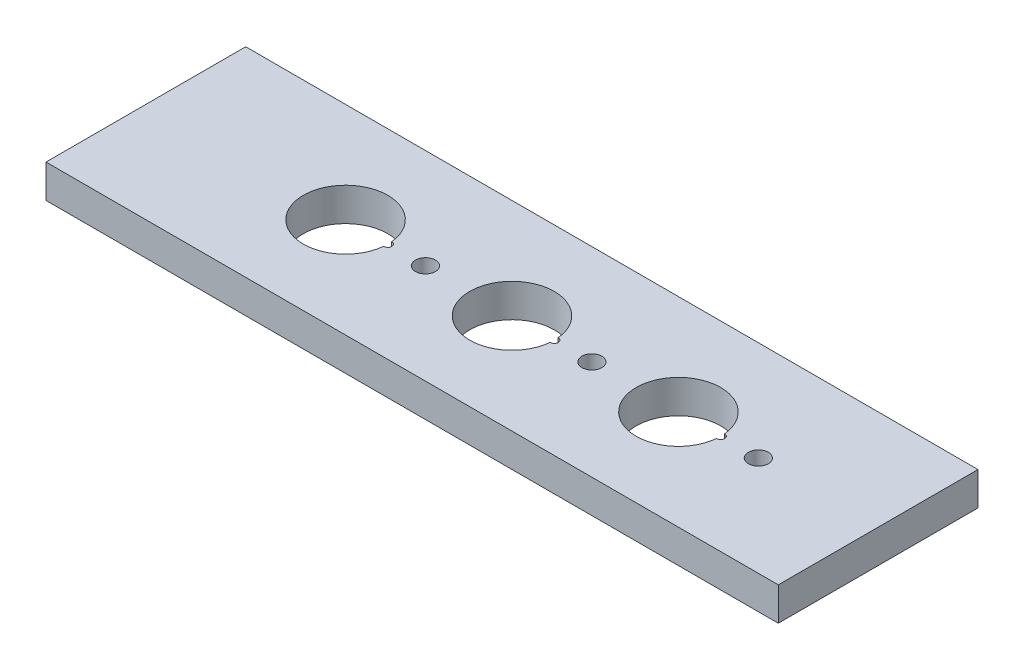
SolidWorks part; units mm, degrees
ref_plane "Front Plane" through (0, 0, 0) normal (0, 0, 1) x (1, 0, 0)
ref_plane "Top Plane" through (0, 0, 0) normal (0, 1, 0) x (1, 0, 0)
ref_plane "Right Plane" through (0, 0, 0) normal (1, 0, 0) x (0, 0, -1)
sketch "Sketch1" plane through (0, 0, 0) normal (0, 1, 0) x (1, 0, 0)
  line L1 (-55, 15) -> (55, 15)
  line L2 (-55, 15) -> (-55, -15)
  line L3 (-55, -15) -> (55, -15)
  line L4 (55, 15) -> (55, -15)
  circle A0 centre (25, 0) radius 6.35 construction
  arc A1 (31.3217, 0.5993) -> (31.3217, -0.5993) centre (31.35, 0) cw
  arc A2 (31.3217, 0.5993) -> (31.3217, -0.5993) centre (25, 0) ccw
  arc A3 (6.3217, 0.5993) -> (6.3217, -0.5993) centre (6.35, 0) cw
  arc A4 (6.3217, 0.5993) -> (6.3217, -0.5993) centre (0, 0) ccw
  arc A5 (-18.6783, 0.5993) -> (-18.6783, -0.5993) centre (-18.65, 0) cw
  arc A6 (-18.6783, 0.5993) -> (-18.6783, -0.5993) centre (-25, 0) ccw
  circle A7 centre (37, 0) radius 1.5
  circle A8 centre (12, 0) radius 1.5
  circle A9 centre (-13, 0) radius 1.5
  point P4 (0, 15)
  point P6 (55, 0)
  dimension "D3" = 12.7
  dimension "D4" = 0.6
  dimension "D7" = 3
  dimension "D1" = 110
  dimension "D2" = 30
  dimension "D6" = 25
  dimension "D8" = 12
  dimension "D5" = 3
  dimension "D9" = 3
extrude "Boss-Extrude1" add sketch "Sketch1" along normal blind 5
